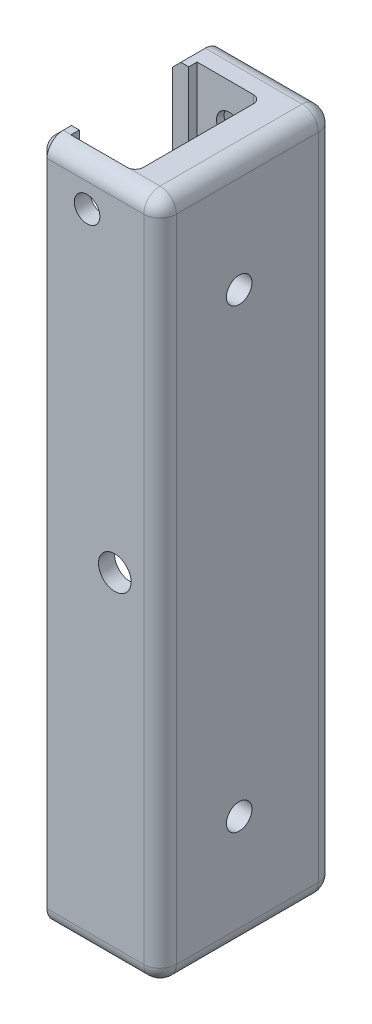
SolidWorks part; units mm, degrees
ref_plane "Front Plane" through (0, 0, 0) normal (0, 0, 1) x (1, 0, 0)
ref_plane "Top Plane" through (0, 0, 0) normal (0, 1, 0) x (1, 0, 0)
ref_plane "Right Plane" through (0, 0, 0) normal (1, 0, 0) x (0, 0, -1)
sketch "Sketch1" plane through (0, 0, 0) normal (0, 1, 0) x (1, 0, 0)
  line L0 (14.225, -12.25) -> (14.225, 12.25)
  line L1 (-6.225, -12.25) -> (6.225, -12.25) construction
  line L2 (-6.225, -12.25) -> (-6.225, 12.25) construction
  line L3 (-6.225, 12.25) -> (6.225, 12.25) construction
  line L4 (6.225, -12.25) -> (6.225, 12.25) construction
  line L5 (-6.225, -12.25) -> (6.225, 12.25) construction
  line L6 (-6.225, 12.25) -> (6.225, -12.25) construction
  line L7 (-6.225, 18.6) -> (6.225, 18.6)
  line L8 (-9.4, -15.425) -> (6.225, -15.425)
  line L9 (-9.4, -15.425) -> (-9.4, 12.25)
  line L10 (-9.4, 12.25) -> (-9.4, 18.6)
  line L11 (-9.4, 18.6) -> (-6.225, 18.6)
  line L12 (6.225, 18.6) -> (14.225, 18.6)
  line L13 (14.225, 18.6) -> (14.225, 12.25)
  line L14 (6.225, -15.425) -> (14.225, -15.425)
  line L15 (14.225, -15.425) -> (14.225, -12.25)
  point P0 (0, 0)
  dimension "D1" = 12.45
  dimension "D2" = 24.5
  dimension "D3" = 8
  dimension "D4" = 6.35
  dimension "D5" = 3.175
extrude "Boss-Extrude1" add sketch "Sketch1" along normal mid plane 133
sketch "Sketch2" plane through (0, 66.5, 0) normal (0, 1, 0) x (1, 0, 0)
  line L0 (14.225, 18.6) -> (-9.4, 18.6) construction
  line L1 (-6.2758, -12.3008) -> (6.2758, -12.3008)
  line L2 (-6.2758, -12.3008) -> (-6.2758, 12.3008)
  line L3 (-6.2758, 12.3008) -> (6.2758, 12.3008)
  line L4 (6.2758, -12.3008) -> (6.2758, 12.3008)
  line L5 (14.225, -15.425) -> (14.225, 18.6) construction
  line L6 (-9.4, -15.425) -> (14.225, -15.425) construction
  line L7 (-9.4, 18.6) -> (-9.4, -15.425) construction
  dimension "D1" = 6.2992
  dimension "D2" = 7.9492
  dimension "D3" = 3.1242
  dimension "D4" = 3.1242
extrude "Cut-Extrude1" cut sketch "Sketch2" against normal offset from surface (120.5 mm away) 54 up to plane "Top Plane" offset beyond the face yes
sketch "Sketch3" plane through (-9.4, 0, 0) normal (-1, 0, 0) x (0, 0, 1)
  line L0 (-18.6, 66.5) -> (15.425, 66.5) construction
  line L1 (10.6625, -50) -> (-10.6625, -50)
  line L2 (10.6625, -50) -> (10.6625, 66.5)
  line L3 (10.6625, 66.5) -> (-10.6625, 66.5)
  line L4 (-10.6625, -50) -> (-10.6625, 66.5)
  line L6 (15.425, 66.5) -> (15.425, -66.5) construction
  line L7 (-18.6, 66.5) -> (-18.6, -66.5) construction
  dimension "D1" = 50
  dimension "D2" = 4.7625
  dimension "D3" = 7.9375
extrude "Cut-Extrude2" cut sketch "Sketch3" against normal up to next
fillet "Fillet1" radius 1.5875 2 edges at (6.2758, 6.25, 12.3008) (6.2758, 6.25, -12.3008)
sketch "Sketch4" plane through (0, -66.5, 0) normal (0, -1, 0) x (1, 0, 0)
  line L1 (3.9687, 11.1125) -> (-3.9688, 11.1125)
  line L2 (3.9687, 11.1125) -> (3.9688, -11.1125)
  line L3 (3.9688, -11.1125) -> (-3.9687, -11.1125)
  line L4 (-3.9688, 11.1125) -> (-3.9687, -11.1125)
  line L5 (3.9687, 11.1125) -> (-3.9687, -11.1125) construction
  line L6 (3.9688, -11.1125) -> (-3.9688, 11.1125) construction
  point P0 (0, 0)
  dimension "D1" = 7.9375
  dimension "D2" = 22.225
extrude "Cut-Extrude3" cut sketch "Sketch4" against normal through all
fillet "Fillet2" radius 3.175 4 edges at (2.4125, 66.5, 15.425) (2.4125, 66.5, -18.6) (2.4125, -66.5, 15.425) (2.4125, -66.5, -18.6)
fillet "Fillet3" radius 1.5875 4 edges at (3.9687, -60.25, 11.1125) (-3.9688, -60.25, 11.1125) (-3.9687, -60.25, -11.1125) (3.9688, -60.25, -11.1125)
chamfer "Chamfer1" distance 1.5875 angle 45 9 edges at (-9.4, 66.5, 11.4563) (-9.4, 65.5701, 14.4951) (-9.4, 0, 15.425) (-9.4, -65.5701, 14.4951) (-9.4, 66.5, -13.0438) (-9.4, -66.5, -1.5875) (-9.4, 65.5701, -17.6701) (-9.4, -65.5701, -17.6701) (-9.4, 0, -18.6)
fillet "Fillet5" radius 3.175 2 edges at (-7.8379, -50, 10.6625) (-7.8379, -50, -10.6625)
sketch "Sketch5" plane through (0, 0, -18.6) normal (0, 0, -1) x (-1, 0, 0)
  line L0 (9.4, 63.325) -> (9.4, -63.325) construction
  circle A0 centre (-5.4, 0) radius 3.175
  dimension "D2" = 6.35
  dimension "D1" = 14.8
extrude "Cut-Extrude4" cut sketch "Sketch5" against normal through all
sketch "Sketch6" plane through (0, 0, 15.425) normal (0, 0, 1) x (1, 0, 0)
  circle A0 centre (5.4, 0) radius 5.588
  dimension "D1" = 11.176
extrude "Cut-Extrude5" cut sketch "Sketch6" against normal offset from surface (19.1724 mm away) 4.1465 from offset 12.7 up to face at (0.623, 4.1667, -12.3008) offset beyond the face yes offset against normal yes
fillet "Fillet6" radius 3.175 1 edges at (10.988, 0, 2.725)
sketch "Sketch7" plane through (6.2758, 0, 0) normal (-1, 0, 0) x (0, 0, 1)
  line L0 (0, -44.45) -> (0, 44.45) construction
  circle A0 centre (0, 44.45) radius 2.4892
  circle A1 centre (0, -44.45) radius 2.4892
  point P4 (0, 0)
  dimension "D1" = 4.9784
  dimension "D2" = 88.9
extrude "Cut-Extrude6" cut sketch "Sketch7" against normal through all
sketch "Sketch8" plane through (6.2758, 0, 0) normal (-1, 0, 0) x (0, 0, 1)
  circle A0 centre (0, -44.45) radius 4.6355
  circle A1 centre (0, 44.45) radius 4.6355
  dimension "D1" = 9.271
extrude "Cut-Extrude7" cut sketch "Sketch8" against normal offset from surface (3.3591 mm away) 3.3592 up to face at (6.2758, 44.45, 2.4892)
sketch "Sketch10" plane through (0, 0, -18.6) normal (0, 0, -1) x (-1, 0, 0)
  line L0 (0, -54) -> (0, 54) construction
  line L1 (0, 54) -> (0, 58.6625) construction
  line L2 (0, 58.6625) -> (0, 63.325) construction
  line L3 (7.8125, 63.325) -> (-14.225, 63.325) construction
  circle A0 centre (0, 58.6625) radius 2.4892
  point P4 (0, 0)
  dimension "D2" = 4.9784
  dimension "D1" = 108
extrude "Cut-Extrude8" cut sketch "Sketch10" against normal through all
sketch "Sketch11" plane through (0, 0, -18.6) normal (0, 0, -1) x (-1, 0, 0)
  circle A0 centre (0, 58.6625) radius 3.9688
  dimension "D1" = 7.9375
extrude "Cut-Extrude9" cut sketch "Sketch11" against normal blind 4.826
sketch "Sketch12" plane through (0, 0, -18.6) normal (0, 0, -1) x (-1, 0, 0)
  line L0 (-7.9, 21) -> (-4.7, 21) construction
  line L1 (-7.9, 21.625) -> (-4.7, 21.625)
  line L2 (-7.9, 20.375) -> (-4.7, 20.375)
  arc A0 (-7.9, 21.625) -> (-7.9, 20.375) centre (-7.9, 21) ccw
  arc A1 (-4.7, 20.375) -> (-4.7, 21.625) centre (-4.7, 21) ccw
  circle A2 centre (-5.4, 0) radius 3.175 construction
  point P2 (-6.3, 21)
  dimension "D4" = 0.625
  dimension "D1" = 21
  dimension "D2" = 2.5
  dimension "D3" = 3.2
extrude "Boss-Extrude3" add sketch "Sketch12" along normal blind 1.5
mirror "Mirror2" about plane through (0, 0, 0) normal (0, 1, 0) of "Boss-Extrude3"
fillet "Fillet7" radius 3.175 4 edges at (14.225, -66.5, -1.5875) (14.225, 66.5, -1.5875) (14.225, 0, 15.425) (14.225, 0, -18.6) tangent propagation no
